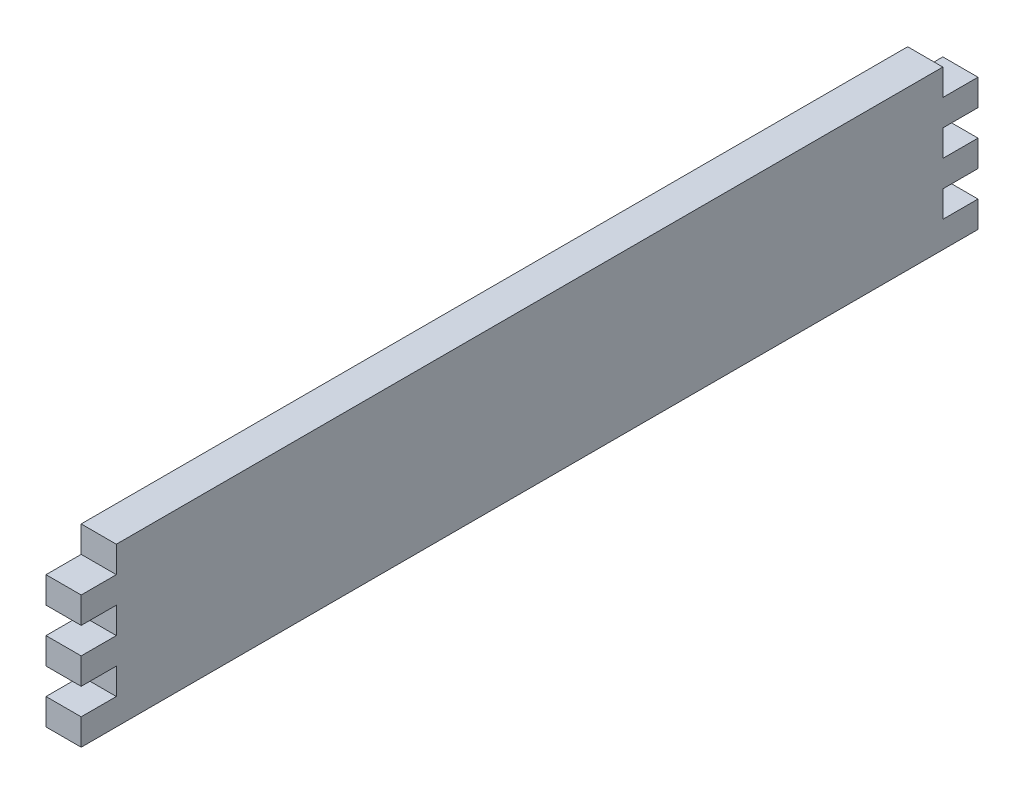
SolidWorks part; units mm, degrees
material "Сосна"
ref_plane "Спереди" through (0, 0, 0) normal (0, 0, 1) x (1, 0, 0)
ref_plane "Сверху" through (0, 0, 0) normal (0, 1, 0) x (1, 0, 0)
ref_plane "Справа" through (0, 0, 0) normal (1, 0, 0) x (0, 0, -1)
sketch "Эскиз1" plane through (0, 0, 0) normal (0, 0, 1) x (1, 0, 0)
  line L0 (0, 0) -> (0, 100)
  line L3 (0, 100) -> (20, 100)
  line L4 (20, 100) -> (20, 10)
  line L5 (20, 10) -> (10, 10)
  line L6 (10, 10) -> (10, 0)
  line L7 (10, 0) -> (0, 0)
  dimension "D1" = 100
  dimension "D2" = 20
  dimension "D3" = 10
  dimension "D4" = 10
extrude "Бобышка-Вытянуть1" add sketch "Эскиз1" along normal blind 470
sketch "Эскиз2" plane through (0, 0, 0) normal (-1, 0, 0) x (0, 0, 1)
  line L0 (470, 100) -> (470, 0) construction
  line L1 (470, 85) -> (490, 85)
  line L2 (470, 85) -> (470, 70)
  line L3 (470, 70) -> (490, 70)
  line L4 (490, 85) -> (490, 70)
  line L5 (470, 100) -> (0, 100) construction
  dimension "D1" = 15
  dimension "D2" = 20
  dimension "D3" = 15
extrude "Бобышка-Вытянуть2" add sketch "Эскиз2" against normal up to surface (20 mm away) up to face at (20, 55, 235)
pattern_linear "Линейный массив1" count 1 spacing 10 along (0, 0, 1) count 3 spacing 30 along (0, -1, 0) of "Бобышка-Вытянуть2"
pattern_linear "Линейный массив2" count 2 spacing 490 along (0, 0, -1) of "Линейный массив1"
